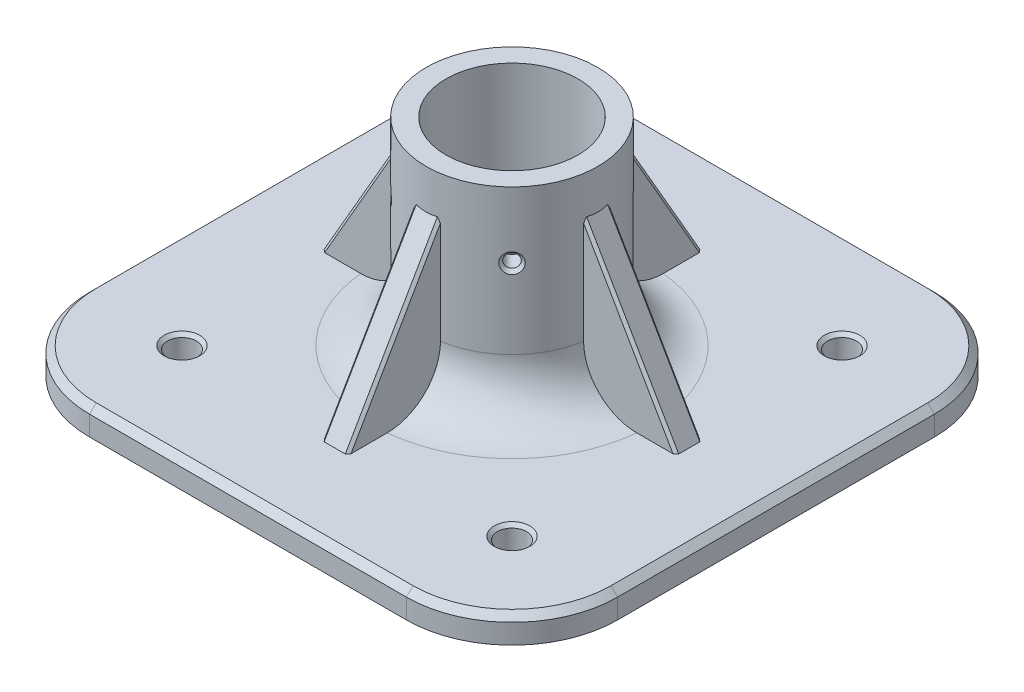
SolidWorks part; units mm, degrees
material "ABS PC"
ref_plane "Front Plane" through (0, 0, 0) normal (0, 0, 1) x (1, 0, 0)
ref_plane "Top Plane" through (0, 0, 0) normal (0, 1, 0) x (1, 0, 0)
ref_plane "Right Plane" through (0, 0, 0) normal (1, 0, 0) x (0, 0, -1)
ref_axis "X Axis" through (-88.99, 0, 0) along (1, 0, 0)
ref_axis "Y Axis" through (0, 55, 0) along (0, -1, 0)
ref_axis "Z Axis" through (0, 0, -88.99) along (0, 0, 1)
sketch "Sketch1" plane through (0, 0, 0) normal (0, 1, 0) x (1, 0, 0)
  line L1 (-100, -100) -> (100, -100)
  line L2 (-100, -100) -> (-100, 100)
  line L3 (-100, 100) -> (100, 100)
  line L4 (100, -100) -> (100, 100)
  line L5 (0, 100) -> (0, -100) construction
  line L6 (-100, 0) -> (100, 0) construction
  point P0 (0, 0)
  dimension "D1" = 200
  dimension "D2" = 200
extrude "Boss-Extrude1" add sketch "Sketch1" along normal blind 10
sketch "Sketch2" plane through (0, 10, 0) normal (0, 1, 0) x (1, 0, 0)
  circle A0 centre (0, 0) radius 32.5
  circle A1 centre (0, 0) radius 25
  dimension "D1" = 50
  dimension "D2" = 65
extrude "Boss-Extrude2" add sketch "Sketch2" along normal blind 75
sketch "Sketch3" plane through (0, 0, 0) normal (0, 0, 1) x (1, 0, 0)
  line L0 (32.5, 70) -> (67.141, 10)
  line L1 (32.5, 10) -> (32.5, 85) construction
  line L2 (-100, 10) -> (100, 10) construction
  dimension "D1" = 60
  dimension "D2" = 60
rib "Rib1" sketch "Sketch3" sketch "Sketch3" thickness 10 extrusion direction parallel to sketch draft on no parameters "D1"=10
pattern_circular "CirPattern1" count 4 over 360 about axis through (0, 85, 0) along (0, -1, 0) of "Rib1"
ref_plane "Set Screw Plane 1" through (-22.981, 0, 22.981) normal (-0.7071, 0, 0.7071) x (0, -1, 0)
ref_plane "Set Screw Plane 2" through (22.981, 0, 22.981) normal (0.7071, 0, 0.7071) x (0, -1, 0)
sketch "Sketch4" plane through (-22.981, 0, 22.981) normal (-0.7071, 0, 0.7071) x (0, -1, 0)
  line L0 (-10, 19.1718) -> (-10, -19.1718) construction
  line L1 (-60, 0) -> (0, 0) construction
  circle A0 centre (-60, 0) radius 3
  dimension "D1" = 6
  dimension "D2" = 50
extrude "Cut-Extrude1" [suppressed] cut sketch "Sketch4" against normal up to next
hole_wizard "M6x1.0 Tapped Hole1" positions "Sketch9" profile "Sketch10" tap size "M6x1.0" standard "ANSI Metric" end condition up to next
sketch "Sketch9" plane through (-22.981, 0, 22.981) normal (-0.7071, 0, 0.7071) x (0, -1, 0)
  point P0 (-60, 0)
sketch "Sketch10" plane through (-22.981, 60, 22.981) normal (0, 1, 0) x (0.7071, 0, 0.7071)
  line L0 (0, 0) -> (0, 7.5)
  line L1 (0, 7.5) -> (2.5, 7.5)
  line L2 (2.5, 7.5) -> (2.5, 1.25)
  line L3 (2.5, 1.25) -> (3.75, 0)
  line L5 (3.75, 0) -> (0, 0)
  line L6 (-2.5, 1.25) -> (-3.75, 0) construction
  line L11 (0, -6.35) -> (0, 107.95) construction
  dimension "Thru Tap Drill Dia." = 5
  dimension "Thru Tap Drill Depth" = 7.5
  dimension "Near C'Sink Dia." = 7.5
  dimension "Near C'Sink Angle" = 90
cosmetic thread "Hole Thread1" parameters "D2"=6
sketch "Sketch5" plane through (22.981, 0, 22.981) normal (0.7071, 0, 0.7071) x (0, -1, 0)
  line L0 (-60, 0) -> (0, 0) construction
  line L1 (-10, 19.1718) -> (-10, -19.1718) construction
  circle A0 centre (-60, 0) radius 3
  dimension "D1" = 50
  dimension "D2" = 6
extrude "Cut-Extrude2" [suppressed] cut sketch "Sketch5" against normal up to next
hole_wizard "M6x1.0 Tapped Hole2" positions "Sketch11" profile "Sketch12" tap size "M6x1.0" standard "ANSI Metric" end condition up to next
sketch "Sketch11" plane through (22.981, 0, 22.981) normal (0.7071, 0, 0.7071) x (0, -1, 0)
  point P0 (-60, 0)
sketch "Sketch12" plane through (22.981, 60, 22.981) normal (0, 1, 0) x (0.7071, 0, -0.7071)
  line L0 (0, 0) -> (0, 7.5)
  line L1 (0, 7.5) -> (2.5, 7.5)
  line L2 (2.5, 7.5) -> (2.5, 1.25)
  line L3 (2.5, 1.25) -> (3.75, 0)
  line L5 (3.75, 0) -> (0, 0)
  line L6 (-2.5, 1.25) -> (-3.75, 0) construction
  line L11 (0, -6.35) -> (0, 107.95) construction
  dimension "Thru Tap Drill Dia." = 5
  dimension "Thru Tap Drill Depth" = 7.5
  dimension "Near C'Sink Dia." = 7.5
  dimension "Near C'Sink Angle" = 90
cosmetic thread "Hole Thread2" parameters "D2"=6
sketch "Sketch6" plane through (0, 10, 0) normal (0, 1, 0) x (1, 0, 0)
  line L1 (-62.5, -62.5) -> (62.5, -62.5) construction
  line L2 (-62.5, -62.5) -> (-62.5, 62.5) construction
  line L3 (-62.5, 62.5) -> (62.5, 62.5) construction
  line L4 (62.5, -62.5) -> (62.5, 62.5) construction
  line L5 (0, 62.5) -> (0, -62.5) construction
  line L6 (-62.5, 0) -> (62.5, 0) construction
  point P0 (0, 0)
  dimension "D1" = 125
  dimension "D2" = 125
hole_wizard "Mounting Holes" positions "Sketch7" profile "Sketch8" hole size "M10" standard "ANSI Metric" end condition up to next
sketch "Sketch7" plane through (0, 10, 0) normal (0, 1, 0) x (1, 0, 0)
  point P0 (-62.5, 62.5)
  point P3 (62.5, 62.5)
  point P6 (62.5, -62.5)
  point P9 (-62.5, -62.5)
sketch "Sketch8" plane through (-62.5, 10, -62.5) normal (1, 0, 0) x (0, 0, 1)
  line L0 (0, 0) -> (0, 10)
  line L1 (0, 10) -> (5.5, 10)
  line L2 (5.5, 10) -> (5.5, 1.25)
  line L3 (5.5, 1.25) -> (6.75, 0)
  line L5 (6.75, 0) -> (0, 0)
  line L6 (-5.5, 1.25) -> (-6.75, 0) construction
  line L11 (0, -6.35) -> (0, 107.95) construction
  dimension "Thru Hole Dia." = 11
  dimension "Thru Hole Depth" = 10
  dimension "Near C'Sink Dia." = 13.5
  dimension "Near C'Sink Angle" = 90
fillet "Fillet1" radius 20 4 edges at (-22.981, 10, -22.981) (22.981, 10, -22.981) (22.981, 10, 22.981) (-22.981, 10, 22.981)
fillet "Fillet2" radius 40 4 edges at (-100, 5, -100) (100, 5, -100) (100, 5, 100) (-100, 5, 100)
chamfer "Chamfer1" distance 2.5 angle 45 8 edges at (-100, 10, 0) (-88.2843, 10, 88.2843) (-88.2843, 10, -88.2843) (0, 10, 100) (0, 10, -100) (88.2843, 10, 88.2843) (88.2843, 10, -88.2843) (100, 10, 0)
chamfer "Chamfer2" distance 1 angle 45 8 edges at (-49.627, 40.3351, -5) (-49.627, 40.3351, 5) (-5, 40.3351, 49.627) (5, 40.3351, 49.627) (49.627, 40.3351, 5) (49.627, 40.3351, -5) (-5, 40.3351, -49.627) (5, 40.3351, -49.627)
